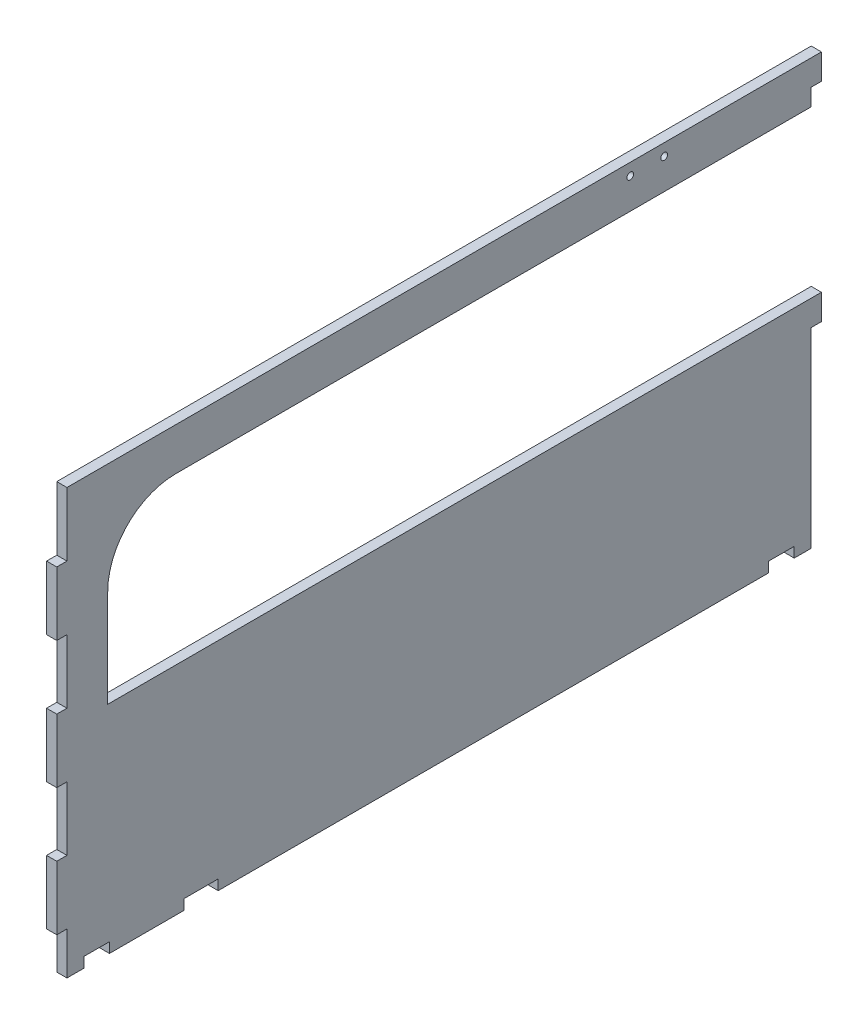
SolidWorks part; units mm, degrees
ref_plane "Front" through (0, 0, 0) normal (0, 0, 1) x (1, 0, 0)
ref_plane "Top" through (0, 0, 0) normal (0, 1, 0) x (1, 0, 0)
ref_plane "Right" through (0, 0, 0) normal (1, 0, 0) x (0, 0, -1)
sketch "Sketch1" plane through (0, 0, 0) normal (1, 0, 0) x (0, 0, -1)
  line L0 (450, 225) -> (450, 250)
  line L1 (0, 0) -> (450, 0)
  line L2 (0, 0) -> (0, 250)
  line L3 (0, 250) -> (450, 250)
  line L4 (450, 0) -> (450, 127.5)
  line L5 (450, 225) -> (30, 225)
  line L7 (450, 127.5) -> (30, 127.5)
  line L8 (30, 225) -> (30, 127.5)
  dimension "D1" = 420
  dimension "D2" = 250
  dimension "D3" = 127.5
  dimension "D4" = 25
  dimension "D5" = 30
extrude "Boss-Extrude1" add sketch "Sketch1" along normal blind 6
sketch "Sketch2" plane through (6, 0, 0) normal (1, 0, 0) x (0, 0, -1)
  line L1 (0, 250) -> (6, 250)
  line L2 (0, 250) -> (0, 212.5)
  line L3 (0, 212.5) -> (6, 212.5)
  line L4 (6, 250) -> (6, 212.5)
  dimension "D1" = 6
  dimension "D2" = 37.5
extrude "Cut-Extrude1" cut sketch "Sketch2" against normal blind 6
pattern_linear "LPattern1" count 4 spacing 75 along (0, -1, 0) of "Cut-Extrude1"
fillet "Fillet1" radius 40 1 edges at (3, 225, -30)
sketch "Sketch3" plane through (0, 0, 0) normal (-1, 0, 0) x (0, 0, 1)
  line L0 (-450, 0) -> (-450, 127.5) construction
  line L1 (-450, 235) -> (-444, 235)
  line L2 (-450, 235) -> (-450, 225)
  line L3 (-450, 225) -> (-444, 225)
  line L4 (-444, 235) -> (-444, 225)
  line L5 (-70, 225) -> (-450, 225) construction
  line L7 (-450, 112.5) -> (-444, 112.5)
  line L8 (-450, 112.5) -> (-450, 0)
  line L9 (-450, 0) -> (-444, 0)
  line L10 (-444, 112.5) -> (-444, 0)
  line L12 (-450, 225) -> (-450, 250) construction
  line L13 (-450, 127.5) -> (-30, 127.5) construction
  line L14 (-6, 0) -> (-450, 0) construction
  dimension "D1" = 6
  dimension "D2" = 10
  dimension "D4" = 15
extrude "Cut-Extrude2" cut sketch "Sketch3" against normal through all
sketch "Sketch4" plane through (0, 0, 0) normal (-1, 0, 0) x (0, 0, 1)
  line L0 (-6, 0) -> (-444, 0) construction
  line L1 (-16, 0) -> (-31, 0)
  line L2 (-16, 0) -> (-16, 6)
  line L3 (-16, 6) -> (-31, 6)
  line L4 (-31, 0) -> (-31, 6)
  line L5 (-6, 62.5) -> (-6, 100) construction
  line L6 (-6, 0) -> (-444, 0) construction
  line L7 (-434, 0) -> (-419, 0)
  line L8 (-434, 0) -> (-434, 6)
  line L9 (-434, 6) -> (-419, 6)
  line L10 (-419, 0) -> (-419, 6)
  line L11 (-444, 0) -> (-444, 112.5) construction
  dimension "D1" = 10
  dimension "D2" = 15
  dimension "D3" = 6
  dimension "D4" = 10
extrude "Cut-Extrude3" cut sketch "Sketch4" against normal through all
sketch "Sketch5" plane through (0, 0, 0) normal (-1, 0, 0) x (0, 0, 1)
  line L0 (-450, 235) -> (-450, 250) construction
  line L1 (-450, 250) -> (-6, 250) construction
  circle A0 centre (-357.5, 243) radius 2
  circle A1 centre (-337.5, 243) radius 2
  dimension "D3" = 4
  dimension "D1" = 92.5
  dimension "D2" = 7
  dimension "D4" = 20
extrude "Cut-Extrude4" cut sketch "Sketch5" against normal through all
sketch "Sketch6" plane through (0, 0, 0) normal (-1, 0, 0) x (0, 0, 1)
  line L0 (-31, 0) -> (-419, 0) construction
  line L1 (-75, 0) -> (-95, 0)
  line L2 (-75, 0) -> (-75, 6)
  line L3 (-75, 6) -> (-95, 6)
  line L4 (-95, 0) -> (-95, 6)
  line L6 (-16, 6) -> (-31, 6) construction
  line L7 (0, 62.5) -> (0, 25) construction
  dimension "D1" = 20
  dimension "D2" = 75
extrude "Cut-Extrude5" cut sketch "Sketch6" against normal through all
